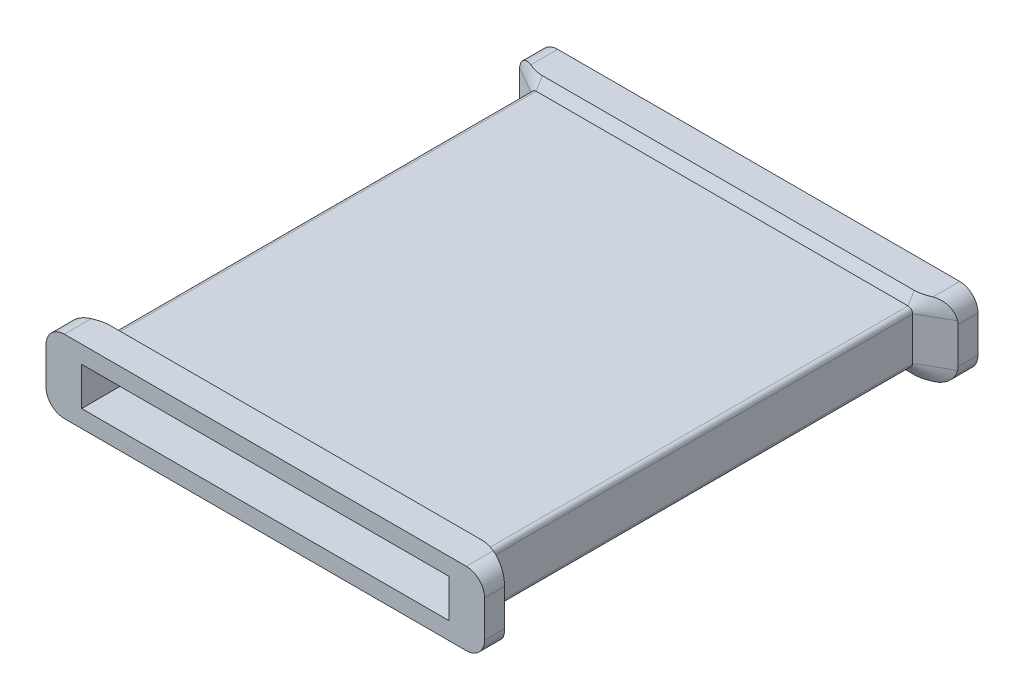
SolidWorks part; units mm, degrees
material "ABS"
ref_plane "Front Plane" through (0, 0, 0) normal (0, 0, 1) x (1, 0, 0)
ref_plane "Top Plane" through (0, 0, 0) normal (0, 1, 0) x (1, 0, 0)
ref_plane "Right Plane" through (0, 0, 0) normal (1, 0, 0) x (0, 0, -1)
sketch "Sketch1" plane through (0, 0, 0) normal (0, 0, 1) x (1, 0, 0)
  line L0 (0, 8) -> (48, 8)
  line L3 (48, 8) -> (48, 0)
  line L4 (48, 0) -> (0, 0)
  line L5 (0, 0) -> (0, 8)
  line L9 (3.9, 6.1) -> (44.1, 6.1)
  line L10 (3.9, 6.1) -> (3.9, 1.9)
  line L11 (3.9, 1.9) -> (44.1, 1.9)
  line L12 (44.1, 6.1) -> (44.1, 1.9)
  dimension "D1" = 1.9
  dimension "D2" = 40.2
  dimension "D4" = 4.2
  dimension "D5" = 1.9
  dimension "D7" = 3.9
  dimension "D8" = 3.9
extrude "Boss-Extrude1" add sketch "Sketch1" along normal blind 54
sketch "Sketch2" plane through (0, 0, 54) normal (0, 0, 1) x (1, 0, 0)
  line L1 (3.65, 6.85) -> (44.35, 6.85)
  line L2 (3.15, 6.35) -> (3.15, 1.65)
  line L3 (3.65, 1.15) -> (44.35, 1.15)
  line L4 (44.85, 6.35) -> (44.85, 1.65)
  line L5 (3.9, 1.9) -> (44.1, 1.9) construction
  line L6 (44.1, 6.1) -> (3.9, 6.1) construction
  line L8 (3.9, 6.1) -> (3.9, 1.9) construction
  line L9 (44.1, 1.9) -> (44.1, 6.1) construction
  arc A0 (3.15, 1.65) -> (3.65, 1.15) centre (3.65, 1.65) ccw
  arc A1 (44.35, 1.15) -> (44.85, 1.65) centre (44.35, 1.65) ccw
  arc A2 (44.35, 6.85) -> (44.85, 6.35) centre (44.35, 6.35) cw
  arc A3 (3.65, 6.85) -> (3.15, 6.35) centre (3.65, 6.35) ccw
  dimension "D1" = 0.5
  dimension "D2" = 0.75
  dimension "D3" = 0.75
  dimension "D4" = 0.75
  dimension "D5" = 0.75
extrude "Cut-Extrude1" cut sketch "Sketch2" against normal offset from surface (50 mm away) 2 from offset 2 flip side to cut up to face at (24, 4, 0) offset against normal yes
fillet "Fillet1" radius 2 8 edges at (48, 8, 53) (48, 0, 53) (48, 0, 1) (48, 8, 1) (0, 0, 1) (0, 8, 1) (0, 0, 53) (0, 8, 53)
chamfer "Chamfer4" distance 2 angle 60 16 edges at (3.15, 4, 52) (3.2964, 1.2964, 52) (3.2964, 6.7036, 52) (24, 1.15, 52) (24, 6.85, 52) (44.7036, 1.2964, 52) (44.7036, 6.7036, 52) (44.85, 4, 52) (3.15, 4, 2) (3.2964, 1.2964, 2) (3.2964, 6.7036, 2) (24, 1.15, 2) (24, 6.85, 2) (44.7036, 1.2964, 2) (44.7036, 6.7036, 2) (44.85, 4, 2) first distance on face at (3.15, 4, 27) first distance on face at (3.3482, 1.3482, 27) first distance on face at (3.3482, 6.6518, 27) first distance on face at (24, 1.15, 27) first distance on face at (24, 6.85, 27) first distance on face at (44.6518, 1.3482, 27) first distance on face at (44.6518, 6.6518, 27) first distance on face at (44.85, 4, 27)
